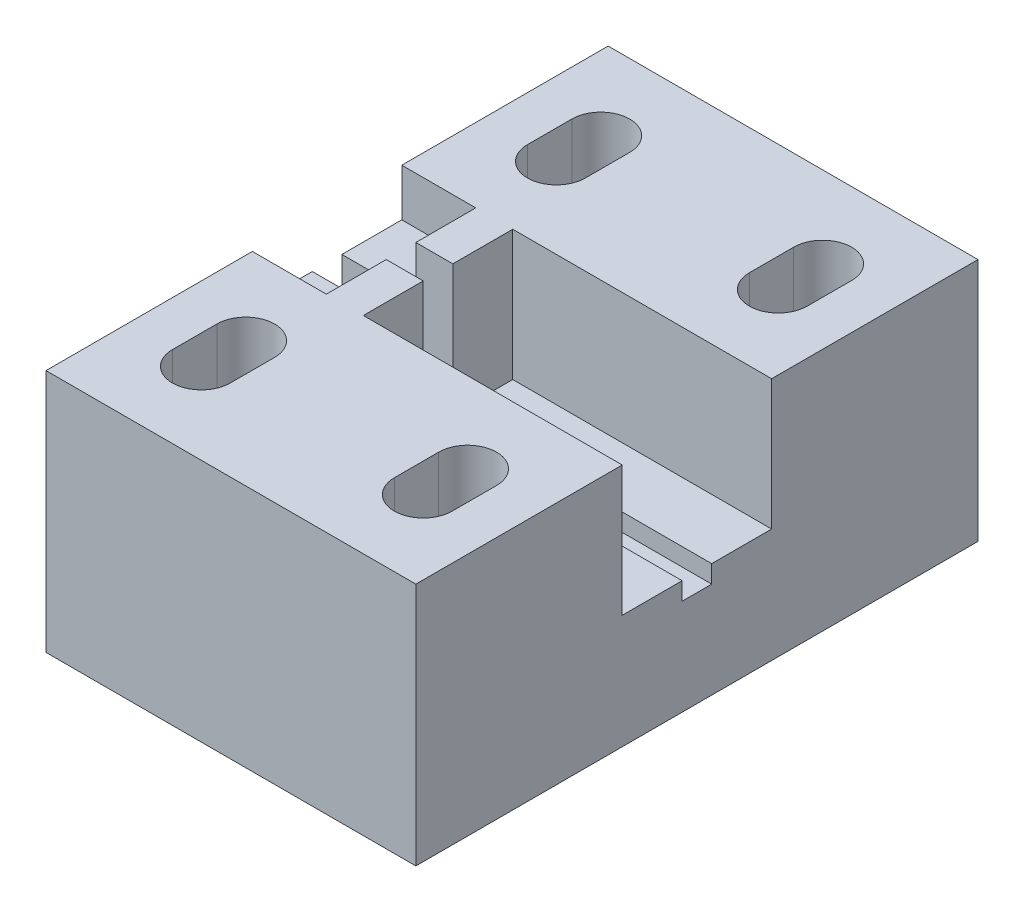
SolidWorks part; units mm, degrees
material "6063-T5"
ref_plane "Front Plane" through (0, 0, 0) normal (0, 0, 1) x (1, 0, 0)
ref_plane "Top Plane" through (0, 0, 0) normal (0, 1, 0) x (1, 0, 0)
ref_plane "Right Plane" through (0, 0, 0) normal (1, 0, 0) x (0, 0, -1)
sketch "Sketch1" plane through (0, 0, 0) normal (0, 1, 0) x (1, 0, 0)
  line L1 (-18493.9467, 11317.1913) -> (-18468.9467, 11317.1913)
  line L2 (-18493.9467, 11317.1913) -> (-18493.9467, 11279.1913)
  line L3 (-18493.9467, 11279.1913) -> (-18468.9467, 11279.1913)
  line L4 (-18468.9467, 11317.1913) -> (-18468.9467, 11279.1913)
  dimension "D1" = 25
  dimension "D2" = 38
extrude "Boss-Extrude1" add sketch "Sketch1" along normal blind 16.5
sketch "Sketch2" plane through (0, 16.5, 0) normal (0, 1, 0) x (1, 0, 0)
  line L0 (-18493.9467, 11298.1913) -> (-18468.9467, 11298.1913)
  line L1 (-18493.9467, 11317.1913) -> (-18493.9467, 11279.1913) construction
  line L2 (-18468.9467, 11279.1913) -> (-18468.9467, 11317.1913) construction
  line L3 (-18488.9467, 11311.6913) -> (-18488.9467, 11308.6913) construction
  line L7 (-18493.9467, 11300.1913) -> (-18493.9467, 11314.1913)
  line L8 (-18493.9467, 11303.2413) -> (-18488.9467, 11303.2413)
  line L9 (-18493.9467, 11303.2413) -> (-18493.9467, 11293.1413)
  line L14 (-18493.9467, 11293.1413) -> (-18488.9467, 11293.1413)
  line L15 (-18488.9467, 11303.2413) -> (-18488.9467, 11293.1413)
  line L16 (-18486.9917, 11311.6913) -> (-18486.9917, 11308.6913)
  line L17 (-18490.9017, 11311.6913) -> (-18490.9017, 11308.6913)
  line L18 (-18488.9467, 11284.6913) -> (-18488.9467, 11287.6913) construction
  line L19 (-18488.9467, 11286.1913) -> (-18488.9467, 11310.1913)
  line L20 (-18488.9467, 11286.1913) -> (-18473.9467, 11286.1913)
  line L21 (-18488.9467, 11310.1913) -> (-18473.9467, 11310.1913)
  line L22 (-18473.9467, 11286.1913) -> (-18473.9467, 11310.1913)
  line L23 (-18488.9467, 11286.1913) -> (-18473.9467, 11310.1913) construction
  line L24 (-18488.9467, 11310.1913) -> (-18473.9467, 11286.1913) construction
  line L25 (-18486.9917, 11284.6913) -> (-18486.9917, 11287.6913)
  line L26 (-18490.9017, 11284.6913) -> (-18490.9017, 11287.6913)
  line L27 (-18481.4467, 11317.1913) -> (-18481.4467, 11279.1913)
  line L28 (-18468.9467, 11317.1913) -> (-18493.9467, 11317.1913) construction
  line L29 (-18493.9467, 11279.1913) -> (-18468.9467, 11279.1913) construction
  line L30 (-18473.9467, 11284.6913) -> (-18473.9467, 11287.6913) construction
  line L31 (-18475.9017, 11284.6913) -> (-18475.9017, 11287.6913)
  line L32 (-18471.9917, 11284.6913) -> (-18471.9917, 11287.6913)
  line L33 (-18473.9467, 11311.6913) -> (-18473.9467, 11308.6913) construction
  line L34 (-18475.9017, 11311.6913) -> (-18475.9017, 11308.6913)
  line L35 (-18471.9917, 11311.6913) -> (-18471.9917, 11308.6913)
  line L37 (-18468.9467, 11303.2413) -> (-18486.4467, 11303.2413)
  line L38 (-18468.9467, 11303.2413) -> (-18468.9467, 11293.1413)
  line L39 (-18468.9467, 11293.1413) -> (-18486.4467, 11293.1413)
  line L40 (-18486.4467, 11303.2413) -> (-18486.4467, 11293.1413)
  line L41 (-18476.4467, 11303.2413) -> (-18468.9467, 11303.2413)
  line L42 (-18476.4467, 11303.2413) -> (-18476.4467, 11304.0883)
  line L43 (-18476.4467, 11304.0883) -> (-18468.9467, 11304.0883)
  line L44 (-18468.9467, 11303.2413) -> (-18468.9467, 11304.0883)
  arc A0 (-18486.9917, 11311.6913) -> (-18490.9017, 11311.6913) centre (-18488.9467, 11311.6913) ccw
  arc A1 (-18490.9017, 11308.6913) -> (-18486.9917, 11308.6913) centre (-18488.9467, 11308.6913) ccw
  arc A2 (-18486.9917, 11284.6913) -> (-18490.9017, 11284.6913) centre (-18488.9467, 11284.6913) cw
  arc A3 (-18490.9017, 11287.6913) -> (-18486.9917, 11287.6913) centre (-18488.9467, 11287.6913) cw
  arc A5 (-18475.9017, 11284.6913) -> (-18471.9917, 11284.6913) centre (-18473.9467, 11284.6913) ccw
  arc A6 (-18471.9917, 11287.6913) -> (-18475.9017, 11287.6913) centre (-18473.9467, 11287.6913) ccw
  arc A7 (-18475.9017, 11311.6913) -> (-18471.9917, 11311.6913) centre (-18473.9467, 11311.6913) cw
  arc A8 (-18471.9917, 11308.6913) -> (-18475.9017, 11308.6913) centre (-18473.9467, 11308.6913) cw
  point P6 (-18490.9467, 11298.1913)
  point P11 (-18488.9467, 11298.1913)
  point P14 (-18488.9467, 11310.1913)
  point P21 (-18488.9467, 11286.1913)
  point P25 (-18481.4467, 11298.1913)
  point P28 (-18486.4467, 11298.1913)
  point P44 (-18473.9467, 11286.1913)
  point P51 (-18473.9467, 11310.1913)
  point P56 (-18476.4467, 11298.1913)
  line M12 (-18493.9467, 11317.1913) -> (-18493.9467, 11279.1913)
  dimension "D7" = 3
  dimension "D8" = 24
  dimension "D9" = 12
  dimension "D10" = 5
  dimension "D14" = 10
  dimension "D15" = 0
  dimension "D2" = 0
  dimension "D3" = 0
  dimension "D4" = 10.1
  dimension "D5" = 5
  dimension "D6" = 3.91
  dimension "D11" = 5
  dimension "D13" = 12.5
  dimension "D16" = 10.1
  dimension "D17" = 0
extrude "6-32 slots" cut sketch "Sketch2" against normal through all contours L16 A1 L17 A0 | L25 A3 L26 A2 | L34 A8 L35 A7 | L31 A6 L32 A5
extrude "lens seat" cut sketch "Sketch2<11>" against normal offset from surface (3.2 mm away) 13.3 contours L15 L8 L7 L0 L19 M12 | L15 L0 L14 L19 M12 region at (-18491.4467, 16.5, -11300.7163) region at (-18491.4467, 16.5, -11295.6663) up to face at (-18473.9467, 0, -11310.1913)
sketch "Sketch2<11>" plane through (0, 16.5, 0) normal (0, 1, 0) x (1, 0, 0) same geometry as "Sketch2"
extrude "lens plate groove" cut sketch "Sketch2<13>" against normal blind 8.8 contours L37 L40 L39 L38
sketch "Sketch2<13>" plane through (0, 16.5, 0) normal (0, 1, 0) x (1, 0, 0) same geometry as "Sketch2"
sketch "Sketch6" plane through (0, 16.5, 0) normal (0, 1, 0) x (1, 0, 0)
  line L6 (-18493.9467, 11303.2413) -> (-18493.9467, 11293.1413) construction
  line L7 (-18493.9467, 11299.1913) -> (-18468.9467, 11299.1913)
  line L8 (-18493.9467, 11299.1913) -> (-18493.9467, 11297.1913)
  line L9 (-18493.9467, 11297.1913) -> (-18468.9467, 11297.1913)
  line L10 (-18468.9467, 11299.1913) -> (-18468.9467, 11297.1913)
  line L11 (-18493.9467, 11298.1913) -> (-18468.9467, 11298.1913) construction
  line L12 (-18468.9467, 11303.2413) -> (-18468.9467, 11293.1413) construction
  point P9 (-18468.9467, 11298.1913)
  dimension "D1" = 0
  dimension "D2" = 0
  dimension "D3" = 2
extrude "alignment groove" cut sketch "Sketch6" against normal blind 10
hole_wizard "#4-40 Tapped Hole2" positions "Sketch9" profile "Sketch10" tap size "#4-40" standard "ANSI Inch" end condition through all
sketch "Sketch9" plane through (0, 7.7, 0) normal (0, 1, 0) x (1, 0, 0)
  line L0 (-18493.9467, 11298.1913) -> (-18468.9467, 11298.1913) construction
  line L1 (-18486.4467, 11303.2413) -> (-18486.4467, 11293.1413) construction
  point P0 (-18481.9467, 11298.1913)
  dimension "D1" = 4.5
sketch "Sketch10" plane through (-18481.9467, 7.7, -11298.1913) normal (1, 0, 0) x (0, 0, 1)
  line L0 (0, 0) -> (0, 7.7)
  line L1 (0, 7.7) -> (1.1303, 7.7)
  line L2 (1.1303, 7.7) -> (1.1303, 0)
  line L5 (1.1303, 0) -> (0, 0)
  line L11 (0, -6.35) -> (0, 107.95) construction
  dimension "Thru Tap Drill Dia." = 2.2606
  dimension "Thru Tap Drill Depth" = 7.7
cosmetic thread "Hole Thread5" parameters "D2"=2.8448
